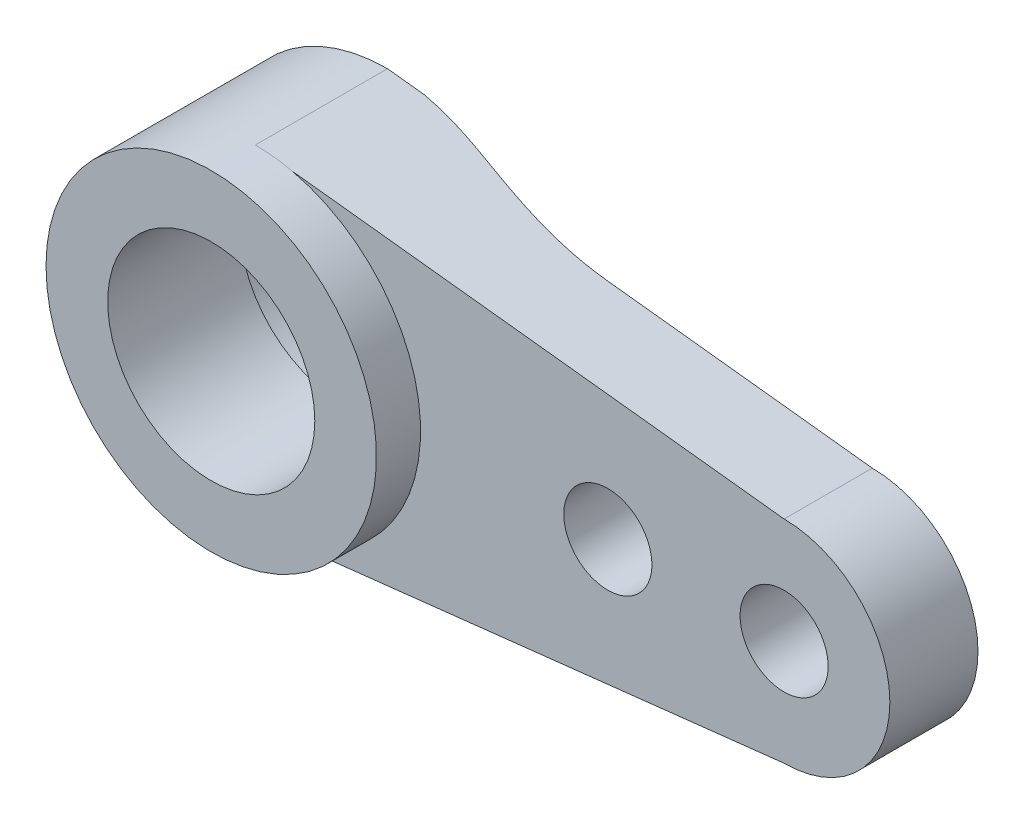
SolidWorks part; units mm, degrees
ref_plane "Front Plane" through (0, 0, 0) normal (0, 0, 1) x (1, 0, 0)
ref_plane "Top Plane" through (0, 0, 0) normal (0, 1, 0) x (1, 0, 0)
ref_plane "Right Plane" through (0, 0, 0) normal (1, 0, 0) x (0, 0, -1)
sketch "Sketch1" plane through (0, 0, 0) normal (0, 0, 1) x (1, 0, 0)
  line L0 (0, 3.75) -> (12, 2.4)
  line L1 (0, -3.75) -> (12, -2.4)
  arc A0 (0.8332, 3.6563) -> (0.8332, -3.6563) centre (0, 0) ccw
  arc A1 (12, -2.4) -> (12, 2.4) centre (12, 0) ccw
  circle A2 centre (0, 0) radius 2.35
  point P9 (0, 0)
  point P10 (8.4363, 3.1217)
  point P11 (0, 0)
  dimension "D1" = 7.5
  dimension "D2" = 4.8
  dimension "D4" = 4.7
  dimension "D3" = 12
extrude "Boss-Extrude1" add sketch "Sketch1" along normal blind 2 contours L1 A1 L0 A0 A2 region at (5.629, 0, 0)
sketch "Sketch2" plane through (0, 0, 2) normal (0, 0, 1) x (1, 0, 0)
  line L2 (0, -3.75) -> (12, -2.4)
  line L3 (12, 2.4) -> (0, 3.75)
  circle A0 centre (0, 0) radius 2.35 construction
  circle A1 centre (0, 0) radius 2.35
  arc A2 (12, -2.4) -> (12, 2.4) centre (12, 0) ccw
  arc A3 (0, 3.75) -> (0, -3.75) centre (0, 0) ccw
  arc A5 (0, 3.75) -> (0, -3.75) centre (0, 0) ccw
  arc A6 (0, 3.75) -> (0, -3.75) centre (0, 0) cw
  dimension "D1" = 0
extrude "Boss-Extrude2" add sketch "Sketch2" along normal blind 1
sketch "Sketch3" plane through (0, 0, 0) normal (0, 0, -1) x (-1, 0, 0)
  line L2 (-12, -2.4) -> (0, -3.75)
  line L3 (0, 3.75) -> (-12, 2.4)
  circle A0 centre (0, 0) radius 2.35 construction
  circle A1 centre (0, 0) radius 2.35
  arc A2 (0, -3.75) -> (0, 3.75) centre (0, 0) ccw
  arc A3 (-12, 2.4) -> (-12, -2.4) centre (-12, 0) ccw
  arc A4 (0, -3.75) -> (0, 3.75) centre (0, 0) ccw
  circle A6 centre (0, 0) radius 2.75
  arc A7 (0, 3.75) -> (0, -3.75) centre (0, 0) ccw
  line M6 (-12, -2.4) -> (0, -3.75)
  arc M7 (0, -3.75) -> (0, 3.75) centre (0, 0) ccw
  line M8 (0, 3.75) -> (-12, 2.4)
  dimension "D2" = 5.5
  dimension "D1" = 0
extrude "Boss-Extrude3" add sketch "Sketch3" along normal blind 1 contours A7 A6 M8 M6 M7 region at (3.6439, 0, 0)
fillet "Fillet1" radius 5 1 edges at (3.75, 0, 0)
sketch "Sketch4" plane through (0, 0, 0) normal (0, 0, -1) x (-1, 0, 0)
  line L0 (0, 0) -> (-8, 0) construction
  circle A3 centre (-12, 0) radius 1
  circle A4 centre (-8, 0) radius 1
  point P3 (-9.3919, 0.7046)
  dimension "D1" = 2
  dimension "D2" = 2
  dimension "D3" = 8
  dimension "D4" = 12
extrude "Cut-Extrude1" cut sketch "Sketch4" against normal up to next
